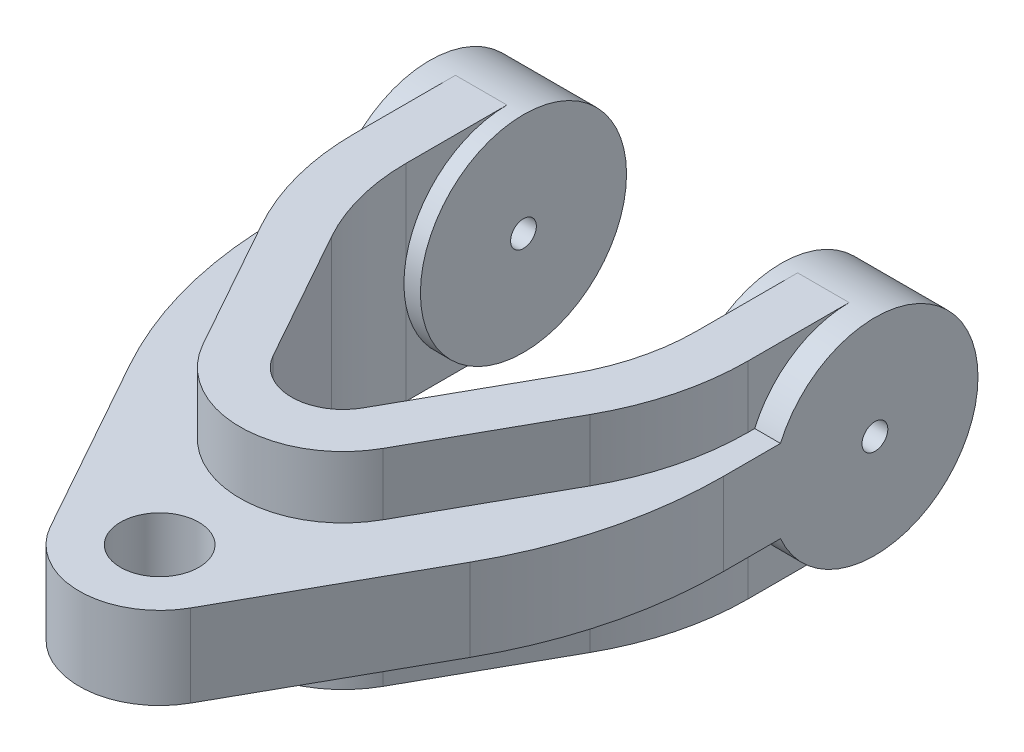
SolidWorks part; units mm, degrees
material "ALUMINUM 6061-T6; 6061-T651"
ref_plane "Front Plane" through (0, 0, 0) normal (0, 0, 1) x (1, 0, 0)
ref_plane "Top Plane" through (0, 0, 0) normal (0, 1, 0) x (1, 0, 0)
ref_plane "Right Plane" through (0, 0, 0) normal (1, 0, 0) x (0, 0, -1)
sketch "Sketch1" plane through (0, 0, 0) normal (0, 1, 0) x (1, 0, 0)
  line L0 (0, -17.4625) -> (0, 17.4625) construction
  line L1 (-7.9375, 0) -> (7.9375, 0) construction
  line L2 (7.9375, 0) -> (11.1125, 0) construction
  line L3 (-7.9375, 0) -> (-11.1125, 0) construction
  line L4 (-11.1125, 0.7937) -> (-11.1125, -0.7938) construction
  line L5 (-11.1125, -0.7938) -> (11.1125, -0.7938) construction
  line L6 (11.1125, -0.7938) -> (11.1125, 0.7937) construction
  line L7 (11.1125, 0.7937) -> (-11.1125, 0.7937) construction
  line L8 (-3.175, -17.4625) -> (3.175, -17.4625) construction
  line L9 (-3.175, 17.4625) -> (3.175, 17.4625) construction
  line L10 (-3.175, 17.4625) -> (-3.175, -17.4625) construction
  line L11 (3.175, 17.4625) -> (3.175, -17.4625) construction
  line L12 (-6.9215, 7.9375) -> (6.9215, 7.9375) construction
  line L13 (6.9215, 7.9375) -> (6.9215, -7.9375) construction
  line L14 (6.9215, -7.9375) -> (-6.9215, -7.9375) construction
  line L15 (-6.9215, -7.9375) -> (-6.9215, 7.9375) construction
  line L16 (8.9535, -9.525) -> (-8.9535, -9.525) construction
  line L17 (-13.716, 6.35) -> (-8.9535, 6.35)
  line L18 (-13.716, 6.35) -> (-13.716, -15.9444)
  line L20 (-8.9535, 6.35) -> (-8.9535, -9.525)
  line L21 (8.9535, 6.35) -> (13.716, 6.35)
  line L22 (8.9535, 6.35) -> (8.9535, -9.525)
  line L24 (13.716, 6.35) -> (13.716, -15.9444)
  line L25 (8.9535, -9.525) -> (2.7723, -20.5976)
  line L26 (-8.9535, -9.525) -> (-2.7723, -20.5976)
  line L27 (0, -17.4625) -> (0, -19.05) construction
  line L28 (0, -19.05) -> (0, -30.353) construction
  line L29 (0, -30.353) -> (0, -35.306) construction
  line L30 (13.716, -15.9444) -> (4.3248, -32.7673)
  line L31 (-13.716, -15.9444) -> (-4.3248, -32.7673)
  circle A0 centre (-7.9375, 0) radius 1.016 construction
  circle A1 centre (7.9375, 0) radius 1.016 construction
  arc A2 (-2.7723, -20.5976) -> (2.7723, -20.5976) centre (0, -19.05) ccw
  arc A3 (-4.3248, -32.7673) -> (4.3248, -32.7673) centre (0, -30.353) ccw
  circle A4 centre (0, -30.353) radius 2.413 construction
  circle A5 centre (0, -30.353) radius 4.953 construction
  point P17 (0, 7.9375)
  point P20 (-6.9215, 0)
  point P40 (0, -22.225)
  point P45 (0, -25.4)
  dimension "D11" = 3.175
  dimension "D14" = 4.826
  dimension "D1" = 3.175
  dimension "D2" = 22.225
  dimension "D3" = 1.5875
  dimension "D4" = 34.925
  dimension "D5" = 6.35
  dimension "D6" = 13.843
  dimension "D7" = 15.875
  dimension "D8" = 6.35
  dimension "D9" = 4.7625
  dimension "D10" = 1.5875
  dimension "D12" = 1.5875
  dimension "D13" = 4.953
  dimension "D15" = 3.175
extrude "Boss-Extrude1" add sketch "Sketch1" along normal blind 2.54 and the other way blind 2.54
sketch "Sketch2" plane through (-8.9535, 0, 0) normal (1, 0, 0) x (0, 0, -1)
  line L0 (6.35, -2.54) -> (6.35, 2.54) construction
  circle A0 centre (0, 0) radius 6.35
extrude "Boss-Extrude2" add sketch "Sketch2" against normal up to surface (4.7625 mm away) and the other way up to vertex (1.016 mm away) up to face at (-13.716, 0, 4.7972) other way up to point (-7.9375, 0, 0)
sketch "Sketch3" plane through (8.9535, 0, 0) normal (-1, 0, 0) x (0, 0, 1)
  circle A1 centre (0, 0) radius 6.35
  circle A2 centre (0, 0) radius 6.35
  dimension "D1" = 0
extrude "Boss-Extrude3" add sketch "Sketch3" against normal up to surface (4.7625 mm away) and the other way up to vertex (1.016 mm away) up to face at (13.716, 0, 4.7972) other way up to point (7.9375, 0, 0)
sketch "Sketch4" plane through (13.716, 0, 0) normal (1, 0, 0) x (0, 0, -1)
  line L0 (0, 0) -> (13.97, 0) construction
  line L1 (3.81, 5.08) -> (13.97, 5.08)
  line L3 (3.81, -5.08) -> (13.97, -5.08)
  line L4 (13.97, 5.08) -> (13.97, -5.08)
  circle A0 centre (0, 0) radius 6.35 construction
  arc A1 (3.81, -5.08) -> (3.81, 5.08) centre (0, 0) ccw
  arc A2 (5.8199, 2.54) -> (-5.8199, 2.54) centre (0, 0) ccw construction
  dimension "D1" = 10.16
extrude "Cut-Extrude1" cut sketch "Sketch4" against normal through all both and the other way through all
sketch "Sketch5" plane through (-8.9535, 0, 0) normal (1, 0, 0) x (0, 0, -1)
  line L0 (0, 6.35) -> (0, -6.35) construction
  arc A0 (-5.8199, -2.54) -> (-5.8199, 2.54) centre (0, 0) ccw construction
sketch "Sketch6" plane through (0, 0, 0) normal (0, 1, 0) x (1, 0, 0)
  line L0 (-8.9535, -9.525) -> (-2.7723, -20.5976) construction
  line L1 (8.9535, -9.525) -> (2.7723, -20.5976) construction
  line L2 (8.9535, 6.35) -> (8.9535, -9.525) construction
  line L3 (-8.9535, 6.35) -> (-8.9535, -9.525) construction
  line L4 (-8.9535, -9.525) -> (-2.7723, -20.5976)
  line L5 (8.9535, -9.525) -> (2.7723, -20.5976)
  line L6 (8.9535, 0) -> (8.9535, -9.525)
  line L7 (-8.9535, 0) -> (-8.9535, -9.525)
  line L8 (-8.9535, 0) -> (-12.1285, 0)
  line L9 (-7.9375, 0) -> (-11.1125, 0) construction
  line L10 (-12.1285, 0) -> (-12.1285, -10.3512)
  line L11 (-12.1285, -10.3512) -> (-5.5446, -22.1452)
  line L12 (5.5446, -22.1452) -> (12.1285, -10.3512)
  line L13 (12.1285, -10.3512) -> (12.1285, 0)
  line L14 (12.1285, 0) -> (8.9535, 0)
  line L15 (7.9375, 0) -> (11.1125, 0) construction
  arc A0 (-2.7723, -20.5976) -> (2.7723, -20.5976) centre (0, -19.05) ccw construction
  arc A1 (-2.7723, -20.5976) -> (2.7723, -20.5976) centre (0, -19.05) ccw
  circle A2 centre (-8.9535, -9.525) radius 3.175 construction
  arc A3 (-5.5446, -22.1452) -> (5.5446, -22.1452) centre (0, -19.05) ccw
  circle A4 centre (8.9535, -9.525) radius 3.175 construction
  dimension "D1" = 3.175
extrude "Boss-Extrude4" add sketch "Sketch6" along normal up to vertex (6.35 mm away) and the other way up to vertex (6.35 mm away) up to point (-8.9535, 6.35, 0) other way up to point (-8.9535, -6.35, 0)
sketch "Sketch7" plane through (13.716, 0, 0) normal (1, 0, 0) x (0, 0, -1)
  circle A0 centre (0, 0) radius 0.7937
  dimension "D1" = 1.5875
extrude "Cut-Extrude2" cut sketch "Sketch7" against normal through all both and the other way through all
fillet "Fillet1" radius 12.7 2 edges at (8.9535, 0, 9.525) (-8.9535, 0, 9.525)
fillet "Fillet2" radius 15.875 4 edges at (12.1285, 4.445, 10.3512) (-12.1285, 4.445, 10.3512) (12.1285, -4.445, 10.3512) (-12.1285, -4.445, 10.3512)
fillet "Fillet3" radius 25.4 2 edges at (-13.716, 0, 15.9444) (13.716, 0, 15.9444)
sketch "Sketch8" plane through (0, 2.54, 0) normal (0, 1, 0) x (1, 0, 0)
  circle A0 centre (0, -30.353) radius 2.413
  dimension "D1" = 4.826
extrude "Cut-Extrude3" cut sketch "Sketch8" against normal through all both
